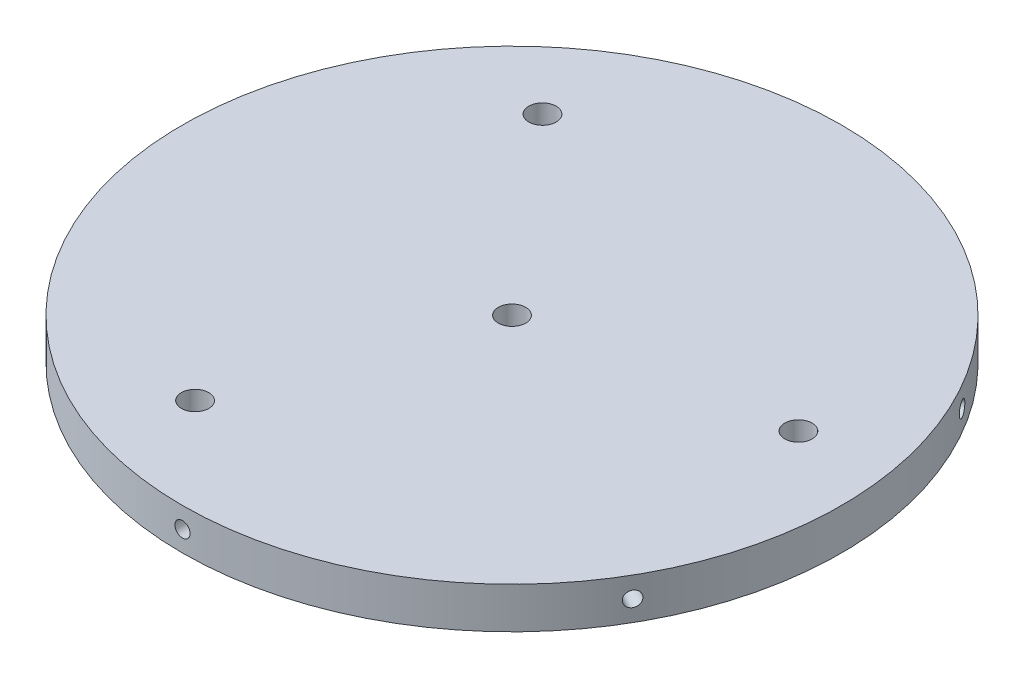
SolidWorks part; units mm, degrees
material "6061-T6 (SS)"
ref_plane "Front Plane" through (0, 0, 0) normal (0, 0, 1) x (1, 0, 0)
ref_plane "Top Plane" through (0, 0, 0) normal (0, 1, 0) x (1, 0, 0)
ref_plane "Right Plane" through (0, 0, 0) normal (1, 0, 0) x (0, 0, -1)
sketch "Sketch1" plane through (0, 0, 0) normal (0, 1, 0) x (1, 0, 0)
  line L0 (0, 0) -> (-50.3682, 60.0265)
  line L1 (0, 0) -> (50.3682, 60.0265)
  line L2 (0, 0) -> (0, 72.1431) construction
  circle A0 centre (0, 0) radius 78.359
  circle A1 centre (0, 0) radius 76.1746
  circle A2 centre (0, 0) radius 76.1746
  dimension "D1" = 156.718
  dimension "D2" = 152.3492
  dimension "D3" = 152.3492
  dimension "D4" = 80
extrude "Boss-Extrude1" add sketch "Sketch1" along normal blind 25.4 contours L2 A2 L1 A0 | L2 A1 L1 A2 | L2 A2 L1 A1 | L2 A0 L1 A2 | A2 L2 A1 L0 | A0 L2 A2 L0 | A2 L2 A0 L0 | A1 L2 A2 L0 region at (0, 0, 13.3592) region at (-23.5316, 0, -29.974) region at (-33.0764, 0, 70.9325) region at (-48.8794, 0, -59.85)
ref_plane "Plane1" through (0, 12.7, 0) normal (0, 1, 0) x (1, 0, 0)
sketch "Sketch6" plane through (0, 25.4, 0) normal (0, 1, 0) x (1, 0, 0)
  circle A0 centre (0, 0) radius 76.1746
  dimension "D1" = 152.3492
extrude "Boss-Extrude5" add sketch "Sketch6" along normal blind 9.525
sketch "Sketch7" plane through (0, 0, 0) normal (0, -1, 0) x (1, 0, 0)
  circle A0 centre (0, 0) radius 76.1746
  dimension "D1" = 152.3492
extrude "Boss-Extrude6" add sketch "Sketch7" along normal blind 9.525
sketch "Sketch8" plane through (0, -9.525, 0) normal (0, -1, 0) x (1, 0, 0)
  circle A0 centre (0, 0) radius 73.025
  dimension "D1" = 146.05
extrude "Cut-Extrude5" cut sketch "Sketch8" against normal up to surface (34.925 mm away) up to face at (0, 25.4, 76.1746)
ref_plane "Plane2" through (0, 0, -76.1746) normal (0, 0, -1) x (-1, 0, 0)
ref_plane "Plane5" through (0, 25.4, 0) normal (0, 1, 0) x (1, 0, 0)
ref_axis "Axis1" through (0, 0, 0) along (0, 1, 0)
sketch "Sketch3" plane through (0, 0, -76.1746) normal (0, 0, -1) x (-1, 0, 0)
  line L4 (76.1746, 0) -> (-76.1746, 0)
  line L5 (-76.1746, -9.525) -> (76.1746, -9.525)
  line L6 (76.1746, 25.4) -> (-76.1746, 25.4)
  line L7 (76.1746, 34.925) -> (-76.1746, 34.925)
  line L8 (0, 34.925) -> (0, 25.4) construction
  line L9 (0, 0) -> (0, -9.525) construction
  circle A0 centre (0, 30.1625) radius 1.75
  circle A1 centre (0, -4.7625) radius 1.75
  point P12 (0, 30.1625)
  point P13 (0, -4.7625)
  point P14 (-77.5445, 179.1871)
  dimension "D1" = 3.5
extrude "Cut-Extrude2" cut sketch "Sketch3" against normal blind 9.525 contours L8 A0 | L8 A0 | L9 A1 | L9 A1 region at (0, 30.1625, -76.1746) region at (0, -4.7625, -76.1746)
extrude "Cut-Extrude3" cut sketch "Sketch1<7>" against normal blind 9.525 from surface contours L2 A1 L1 A2 | A1 L2 A2 L0 | A2 L2 A0 L0 | L2 A2 L1 A0 region at (-23.5316, 0, -29.974) region at (-48.8794, 0, -59.85) starting at plane "Plane5"
sketch "Sketch1<7>" plane through (0, 0, 0) normal (0, 1, 0) x (1, 0, 0) same geometry as "Sketch1"
pattern_circular "CirPattern2" count 3 over 360 about axis through (0, 0, 0) along (0, 1, 0) of "Cut-Extrude3"
ref_plane "Plane3" through (0, 34.925, 0) normal (0, 1, 0) x (1, 0, 0)
sketch "Sketch4" plane through (0, 34.925, 0) normal (0, 1, 0) x (1, 0, 0)
  circle A0 centre (0, 0) radius 73.025
  dimension "D1" = 146.05
extrude "Boss-Extrude4" add sketch "Sketch4" against normal blind 9.525
pattern_circular "CirPattern3" count 6 over 360 about axis through (0, 0, 0) along (0, 1, 0) of "Cut-Extrude2"
sketch "Sketch9" plane through (0, 34.925, 0) normal (0, 1, 0) x (1, 0, 0)
  line L0 (0, 0) -> (-26.8004, -73.6334) construction
  circle A0 centre (0, 0) radius 3.175
  circle A1 centre (-19.5465, -53.7034) radius 3.175
  circle A2 centre (-36.7353, 43.7794) radius 3.175
  circle A3 centre (56.2818, 9.924) radius 3.175
  point P15 (0, 0)
  dimension "D1" = 6.35
  dimension "D2" = 6.35
  dimension "D3" = 57.15
  dimension "D5" = 3
extrude "Cut-Extrude6" cut sketch "Sketch9" against normal through all
sketch "Sketch10" plane through (0, 25.4, 0) normal (0, 1, 0) x (1, 0, 0)
  circle A0 centre (0, 0) radius 82.3228
extrude "Cut-Extrude7" cut sketch "Sketch10" against normal through all
equation "\"AB_Coupler_OD_Length\"= 1in"
equation "\"AB_Coupling_Section_Length\"= 0.375in"
equation "\"AB_Coupler_Length\"= \"AB_Coupler_OD_Length\" + \"AB_Coupling_Section_Length\" * 2"
equation "\"Cutout_Angle\" = 80"
equation "\"AB_Coupler_Num_Screws\"= 6"
equation "\"Num_Cutouts\" = 3"
equation "\"AB_Coupler_OD\"= 6.17in"
equation "\"AB_Coupler_ID\"= 5.75in"
equation "\"AB_Coupler_Surface_Diameter\"= 5.998in"
equation "\"D2@Sketch1\"=\"Bodytube_ID\""
equation "\"AB_Coupling_Screw_Diameter\"= 0.1065in"
equation "\"Aft_Section_Length\"= 39in"
equation "\"Aft_Lower_Length\"= 22in"
equation "\"Aft_Upper_Length\"= \"Aft_Section_Length\" - \"Aft_Lower_Length\" - \"AB_Coupler_OD_Length\""
equation "\"Mid_Coupler_Length\"= 13in"
equation "\"Lead_Screw_Dist\" = 2.25in"
equation "\"Lead_Screw_Diam\" = (27/64)*1in"
equation "\"Lead_Screw_Length\" = (\"Mid_Coupler_Length\" + 2*0.375in + 2*0.5in)"
equation "\"Bodytube_OD\" = 6.17in"
equation "\"Paddle_Pin_Offset\" = .25in"
equation "\"Bodytube_ID\" = 5.998in"
equation "\"Paddle_Pin_Radius\" = 2.25in"
equation "\"D1@Sketch4\"=\"AB_Coupler_ID\""
equation "\"D1@Sketch6\"=\"AB_Coupler_Surface_Diameter\""
equation "\"D1@Boss-Extrude5\"=\"AB_Coupling_Section_Length\""
equation "\"D1@Sketch7\"=\"AB_Coupler_Surface_Diameter\""
equation "\"D1@Boss-Extrude6\"=\"AB_Coupling_Section_Length\""
equation "\"D1@Sketch8\"=\"AB_Coupler_ID\""
equation "\"D3@Sketch9\"=\"Paddle_Pin_Radius\""
